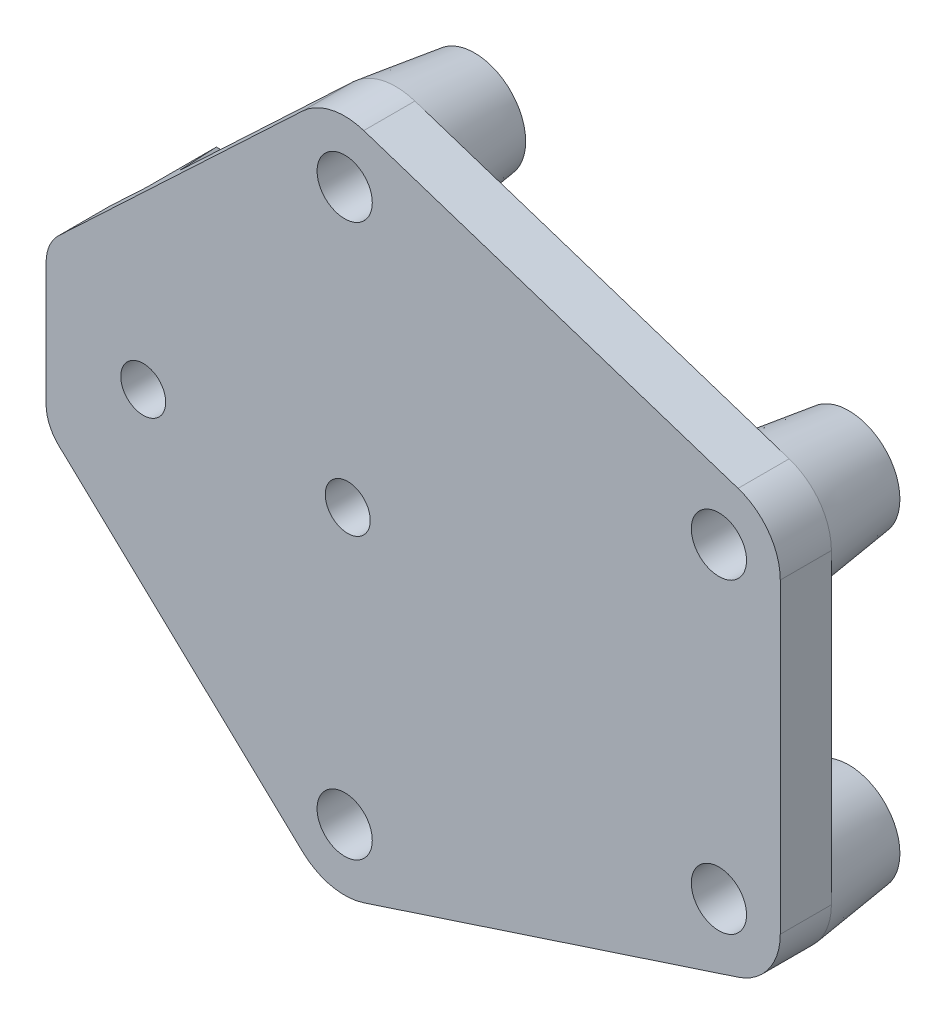
SolidWorks part; units mm, degrees
note: '?' marks a value the reader was unsure of. The reader was unsure of these and kept them because the rebuilt part matched: shared geometry of "草图4<3>", "草图1<4>".
ref_plane "前视基准面" through (0, 0, 0) normal (0, 0, 1) x (1, 0, 0)
ref_plane "上视基准面" through (0, 0, 0) normal (0, 1, 0) x (1, 0, 0)
ref_plane "右视基准面" through (0, 0, 0) normal (1, 0, 0) x (0, 0, -1)
sketch "草图1" plane through (0, 0, 0) normal (0, 0, 1) x (1, 0, 0)
  line L0 (-612.4365, 0) -> (30009.3904, 0) construction
  line L1 (-611.4109, 10) -> (30010.416, 10) construction
  line L2 (-607.9921, -10) -> (30013.8348, -10) construction
  line L3 (0, -612.4365) -> (0, 30009.3904) construction
  line L4 (-10, -612.4365) -> (-10, 30009.3904) construction
  line L5 (10, -614.6741) -> (10, 30007.1528) construction
  line L6 (-24.3, 27) -> (-24.3, -27) construction
  line L7 (-16.4307, 32.7014) -> (20.1693, 20.7014)
  line L8 (24.3, 15) -> (24.3, -15)
  line L9 (-32, -12.3) -> (-42.6472, -12.3)
  line L10 (-32, 12.3) -> (-42.6472, 12.3)
  line L11 (-32, 12.3) -> (-13, 12.3)
  line L12 (-32, 10.3) -> (-13, 10.3)
  line L13 (-13, 12.3) -> (-13, 10.3)
  line L14 (20.1693, -20.7014) -> (-16.4307, -32.7014)
  line L15 (-32, -10.3) -> (-13, -10.3)
  line L16 (-32, -12.3) -> (-13, -12.3)
  line L17 (-13, -12.3) -> (-13, -10.3)
  line L18 (-42.6472, 12.3) -> (-42.6472, 10.3)
  line L19 (-33.5, 10) -> (-33.5, -10) construction
  line L20 (-47.5, 6) -> (-47.5, -6)
  line L21 (-42.6472, 10.3) -> (-32, 10.3)
  line L22 (-42.6472, -12.3) -> (-42.6472, -10.3)
  line L23 (-22.415, 31.3666) -> (-46.2433, 8.911)
  line L24 (-22.415, -31.3666) -> (-46.2433, -8.911)
  line L25 (-42.6472, -10.3) -> (-32, -10.3)
  circle A0 centre (18.3, 27) radius 11.5 construction
  circle A1 centre (-18.3, 27) radius 11.5 construction
  circle A2 centre (-18.3, -27) radius 11.5 construction
  circle A3 centre (18.3, 15) radius 11.5 construction
  circle A4 centre (18.3, 15) radius 2.7
  circle A5 centre (-18.3, 27) radius 6
  circle A6 centre (-16, 14) radius 1.7 construction
  circle A7 centre (18.3, 15) radius 5 construction
  circle A8 centre (-18.3, 27) radius 2.7
  circle A9 centre (-18.3, -27) radius 2.7
  circle A10 centre (-18.3, 27) radius 5 construction
  circle A11 centre (-18.3, -27) radius 5 construction
  circle A12 centre (18.3, 15) radius 6
  circle A13 centre (18.3, -15) radius 5 construction
  circle A14 centre (-16, -14) radius 1.7 construction
  circle A15 centre (-18.3, -27) radius 6
  circle A16 centre (-18, 0) radius 2.2
  circle A17 centre (-38, 0) radius 2.2
  circle A18 centre (-31, 18) radius 2.2 construction
  circle A19 centre (-31, -18) radius 2.2 construction
  circle A20 centre (18.3, -15) radius 11.5 construction
  circle A21 centre (18.3, -15) radius 6
  circle A22 centre (18.3, -15) radius 2.7
  circle A23 centre (-18, 0) radius 4 construction
  arc A26 (-47.5, -6) -> (-43.525, -9.9999) centre (-43.5, -6) ccw
  arc A27 (-47.5, 6) -> (-43.2629, 9.993) centre (-43.5, 6) cw
  point P48 (-31.5, 0)
  point P54 (-31.5, 0)
  point P72 (-43.5893, 0)
  point P82 (-47.5, -10)
  point P85 (-47.5, 10)
  dimension "D5" = 23
  dimension "D6" = 27
  dimension "D7" = 15
  dimension "D9" = 12
  dimension "D10" = 8
  dimension "D11" = 5.4
  dimension "D12" = 10
  dimension "D8" = 4.4
  dimension "D23" = 3.4
  dimension "D24" = 4.4
  dimension "D35" = 4
  dimension "D1" = 20
  dimension "D2" = 10
  dimension "D3" = 20
  dimension "D4" = 10
  dimension "D13" = 18.3
  dimension "D14" = 6
  dimension "D15" = 12
  dimension "D16" = 2
  dimension "D17" = 20.6
  dimension "D18" = 20
  dimension "D19" = 14.3
  dimension "D20" = 24.6
  dimension "D21" = 16
  dimension "D22" = 4
  dimension "D25" = 8
  dimension "D26" = 21
  dimension "D28" = 13
  dimension "D29" = 5
  dimension "D34" = 14
extrude "凸台-拉伸1" add sketch "草图1" along normal blind 5
ref_axis "基准轴1" through (-18.3, 27, 5) along (0, 0, -1)?
ref_axis "基准轴2" through (18.3, 15, 5) along (0, 0, -1)?
ref_plane "基准面2" through (6.2169, 18.9617, 0) normal (-0.3116, -0.9502, 0) x (-0.9502, 0.3116, 0)
sketch "草图4" plane through (6.2169, 18.9617, 0) normal (-0.3116, -0.9502, 0) x (-0.9502, 0.3116, 0)
  line L1 (-7.7159, 7.7) -> (-10.0159, 7.7)
  line L2 (25.8011, 0) -> (25.8011, 29798.822) construction
  line L3 (-6.7159, 0) -> (-7.7159, 7.7)
  line L4 (-10.0159, 0) -> (-6.7159, 0)
  line L5 (-10.0159, 7.7) -> (-10.0159, 0)
  line L10 (25.8011, -5) -> (25.8011, 0) construction
  line L11 (-12.7159, -4.4528) -> (-12.7159, 29794.3692) construction
  line L12 (-12.7159, -5) -> (-12.7159, 0) construction
  line L13 (25.8011, 0) -> (28.5011, 0) construction
  line L14 (31.0717, 0) -> (25.8011, 0) construction
  line L16 (28.5011, 0) -> (31.8011, 0)
  line L17 (31.8011, 0) -> (30.8011, 7.7)
  line L18 (30.8011, 7.7) -> (28.5011, 7.7)
  line L19 (28.5011, 7.7) -> (25.8011, 7.7) construction
  line L20 (28.5011, 7.7) -> (28.5011, 0)
  line L21 (25.8011, 7.7) -> (25.8011, 0) construction
  point P7 (0, 0)
  dimension "D2" = 2
  dimension "D3" = 5
  dimension "D7" = 2.7
  dimension "D8" = 6
  dimension "D9" = 7.7
  dimension "D10" = 5
revolve "旋转1" add sketch "草图4" angle 360 about L11
revolve "旋转2" add sketch "草图4<3>" angle 360 about L2
sketch "草图4<3>" plane through (6.2169, 18.9617, 0) normal (-0.3116, -0.9502, 0) x (-0.9502, 0.3116, 0) same geometry as "草图4"
mirror "镜向1" about plane through (0, 0, 0) normal (0, 1, 0) of "旋转2", "旋转1"
extrude "凸台-拉伸2" add sketch "草图1<4>" against normal blind 6.8
sketch "草图1<4>" plane through (0, 0, 0) normal (0, 0, 1) x (1, 0, 0) same geometry as "草图1"
chamfer "倒角1" distance 3 distance2 6.8 1 edges at (-27.8236, 12.3, 0)
chamfer "倒角2" distance 6.8 distance2 3 1 edges at (-27.8236, -12.3, 0)
sketch "草图5" [suppressed] plane through (0, 0, 0) normal (0, 0, -1) x (-1, 0, 0)
  line L0 (39.5, 5) -> (39.5, -5) construction
  line L1 (41, 5) -> (41, -5)
  line L2 (38, 5) -> (38, -5)
  arc A0 (41, 5) -> (38, 5) centre (39.5, 5) ccw
  arc A1 (38, -5) -> (41, -5) centre (39.5, -5) ccw
  circle A2 centre (39.5, -5) radius 1.5 construction
  point P4 (39.5, 0)
extrude "切除-拉伸1" [suppressed] cut sketch "草图5" against normal blind 2.5
